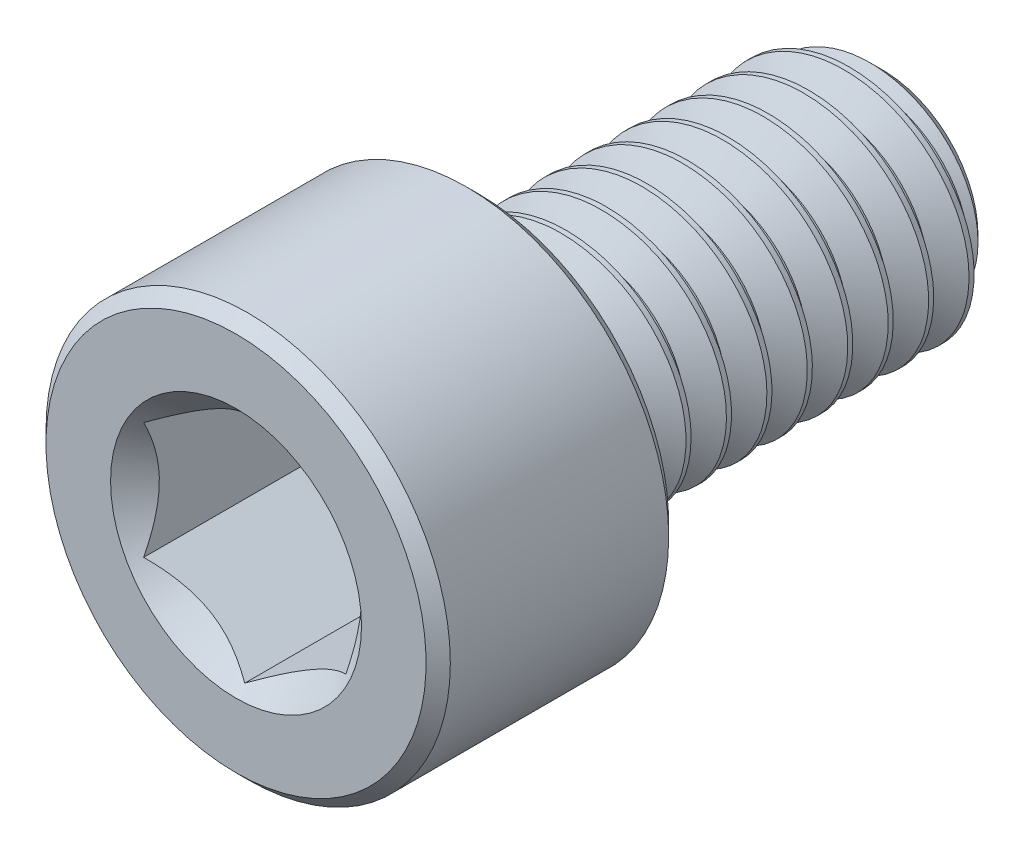
SolidWorks part; units mm, degrees
ref_plane "Front Plane" through (0, 0, 0) normal (0, 0, 1) x (1, 0, 0)
ref_plane "Top Plane" through (0, 0, 0) normal (0, 1, 0) x (1, 0, 0)
ref_plane "Right Plane" through (0, 0, 0) normal (1, 0, 0) x (0, 0, -1)
sketch "Sketch1" plane through (0, 0, 0) normal (1, 0, 0) x (0, 0, -1)
  line L0 (-8, 0) -> (8, 0) construction
  line L1 (8, 0) -> (8, 2.3505) construction
  line L2 (8, 2.3505) -> (7.3505, 3) construction
  line L3 (7.3505, 3) -> (7.25, 3) construction
  line L4 (7.25, 3) -> (-2, 3) construction
  line L5 (-2, 3) -> (-2, 5) construction
  line L6 (-2, 5) -> (-8, 5) construction
  line L7 (-8, 5) -> (-8, 0) construction
  line L8 (8, 2.3505) -> (8, 3) construction
  line L9 (7.9375, 3.1083) -> (8.4375, 2.2422) construction
  line L10 (8.4375, 2.2422) -> (8.9375, 3.1083) construction
  line L11 (8.9375, 3.1083) -> (7.9375, 3.1083) construction
  line L12 (8.4375, 3.1083) -> (8.4375, 3) construction
  line L13 (8.4375, 2.2422) -> (8.4375, 2.3505) construction
  line L14 (8.375, 2.3505) -> (8.5, 2.3505) construction
  line L15 (8, 3) -> (8.875, 3) construction
  line L16 (7.9687, 3.0541) -> (8.9063, 3.0541) construction
  line L17 (8, 0) -> (8, -3) construction
  line L18 (-2.3, 5) -> (-2, 4.7) construction
  line L19 (-7.7, 5) -> (-8, 4.7) construction
  line L20 (-2, 3) -> (-2, 0) construction
  line L21 (-2, 1.5) -> (1.3333, 1.5) construction
  line L22 (1.3333, 1.5) -> (4.6667, 1.5) construction
  line L23 (4.6667, 1.5) -> (8, 1.5) construction
  line L24 (1.3333, 1.5) -> (1.3333, 3) construction
  line L25 (1.3333, 3) -> (1.3333, 5) construction
  line L26 (4.6667, 1.5) -> (4.6667, 5) construction
  point P0 (-8, 2.5)
  point P3 (5.5, 3)
  point P4 (0, 0)
  point P18 (4.6667, 3)
  point P22 (8.4375, 2.3505)
  point P24 (7.25, 3)
  point P25 (8.4375, 3)
  point P28 (8.4375, 3.0541)
  point P29 (5.5, -3)
  point P30 (1.3333, 3)
  point P31 (-5, 5)
  point P37 (-3.05, 5)
  point P38 (-7.55, 5)
  point P45 (1.3333, 1.5)
  point P46 (4.6667, 1.5)
  dimension "D2" = 0.125
  dimension "D7" = 0.3
  dimension "D8" = 0.3
  dimension "D9" = 0.3
  dimension "D10" = 0.15
  dimension "D11" = 0.75
  dimension "Drive Size" = 5
  dimension "Head Diameter" = 10
  dimension "Head Height" = 6
  dimension "Thread Pitch" = 1
  dimension "Thread Dia" = 6
  dimension "Length" = 10
  dimension "D12" = 0.75
  dimension "D4" = 2.5
  dimension "D3" = 45
sketch "Sketch2" plane through (0, 0, 0) normal (1, 0, 0) x (0, 0, -1)
  line L0 (-8, 0) -> (-8, 4.7)
  line L1 (-7.7, 5) -> (-2.3, 5)
  line L2 (-2, 4.7) -> (-2, 3.3)
  line L4 (7.3505, 3) -> (8, 2.3505)
  line L5 (8, 2.3505) -> (8, 0)
  line L6 (-2, 5) -> (-8, 5) construction
  line L7 (8, 0) -> (-8, 0)
  line L8 (-7.7, 5) -> (-8, 4.7) construction
  line L10 (-7.7, 5) -> (-8, 4.7)
  line L14 (-2.3, 5) -> (-2, 4.7) construction
  line L16 (-2.3, 5) -> (-2, 4.7)
  line L17 (-2, 3) -> (-2, 5) construction
  line L19 (-1.7, 3) -> (7.3505, 3)
  line L20 (7.25, 3) -> (-2, 3) construction
  arc A1 (-2, 3.3) -> (-1.7, 3) centre (-1.7, 3.3) ccw
  dimension "D3" = 0.3
revolve "Revolve1" add sketch "Sketch2" angle 360 about L7
sketch "Sketch3" plane through (0, 0, 8) normal (0, 0, 1) x (1, 0, 0)
  line L1 (2.5, -1.4434) -> (2.5, 1.4434)
  line L2 (2.5, 1.4434) -> (0, 2.8868)
  line L3 (0, 2.8868) -> (-2.5, 1.4434)
  line L4 (-2.5, 1.4434) -> (-2.5, -1.4434)
  line L5 (-2.5, -1.4434) -> (0, -2.8868)
  line L6 (0, -2.8868) -> (2.5, -1.4434)
  circle A0 centre (0, 0) radius 2.5 construction
  circle A1 centre (0, 0) radius 5 construction
  circle A2 centre (0, 0) radius 5 construction
  circle A3 centre (0, 0) radius 2.8868 construction
  point P13 (0, 0)
  dimension "D1" = 5.7735
extrude "Cut-Extrude1" cut sketch "Sketch3" against normal offset from surface (5 mm away) 1 up to face at (0, 4.7, 2)
sketch "Sketch4" plane through (0, 0, 8) normal (0, 0, 1) x (1, 0, 0)
  circle A0 centre (0, 0) radius 3.1033
  dimension "D1" = 6.2065
extrude "Cut-Extrude2" cut sketch "Sketch4" against normal up to vertex (3 mm away) draft 45 up to point (0, 5, 5)
sketch "Sketch11" plane through (0, 0, 0) normal (1, 0, 0) x (0, 0, -1)
  line L0 (-8, 0) -> (8, 0) construction
  line L1 (-8, 0) -> (8, 0) construction
  line L2 (-0.125, 0) -> (-0.125, 3) construction
  line L3 (7.25, 3) -> (-2, 3) construction
  line L4 (6.125, 0) -> (6.125, 3) construction
  line L6 (8, 2.3505) -> (8, 3) construction
  point P2 (-0.125, 0)
  point P3 (6.125, 0)
  dimension "D1" = 1.875
  dimension "D2" = 1.875
sketch "Sketch6" plane through (0, 0, -8) normal (0, 0, -1) x (-1, 0, 0)
  circle A0 centre (0, 0) radius 3
curve "Helix/Spiral1" pitch 1 height 11 turns 11
sketch "Sketch10" plane through (0, 0, 0) normal (1, 0, 0) x (0, 0, -1)
  line L0 (-1.7, -5) -> (-1.7, 5)
  line L5 (-8, 0) -> (8, 0) construction
  line L6 (-1.7, 3) -> (-1.7, -3) construction
  point P3 (-1.7, 0)
split "Split1" trim tools "Sketch10" bodies to split 106 resulting bodies 114 115
sketch "Sketch7" plane through (0, 0, 0) normal (1, 0, 0) x (0, 0, -1)
  line L0 (7.9687, 3.0541) -> (8.9063, 3.0541)
  line L1 (8.9063, 3.0541) -> (8.5, 2.3505)
  line L2 (8.5, 2.3505) -> (8.375, 2.3505)
  line L3 (8.375, 2.3505) -> (7.9687, 3.0541)
sweep "Cut-Sweep1" cut profiles "Sketch7" path "Helix/Spiral1" align with end faces yes
sketch "Sketch8" plane through (0, 0, 0) normal (1, 0, 0) x (0, 0, -1)
  line L0 (-2, 0) -> (-2, 3)
  line L1 (-1.7, -3) -> (-1.7, 3) construction
  line L2 (-2, 3) -> (-1.7, 3)
  line L4 (-1.7, 3) -> (0.0321, 0)
  line L5 (0.0321, 0) -> (-2, 0)
  line L6 (7.25, 3) -> (-2, 3) construction
  line L7 (-8, 0) -> (8, 0) construction
  dimension "D1" = 60
revolve "Revolve2" add sketch "Sketch8" angle 360 about L5
equation "\"D2@Sketch1\" = \"Thread Pitch@Sketch1\" / 8"
equation "\"D4@Helix/Spiral1\" = \"Thread Pitch@Sketch1\""
equation "\"D7@Sketch1\" = \"Head Height@Sketch1\" * .05"
equation "\"D8@Sketch1\"=\"D7@Sketch1\""
equation "\"D9@Sketch1\"=\"D7@Sketch1\""
equation "\"D10@Sketch1\"=\"D7@Sketch1\"/2"
equation "\"D11@Sketch1\"=\"D10@Sketch1\"*5"
equation "\"D4@Sketch1\"=\"Thread Pitch@Sketch1\"*2.5"
equation "\"D12@Sketch1\"=\"Thread Pitch@Sketch1\"*.75"
equation "\"D3@Helix/Spiral1\"=\"Length@Sketch1\"+\"Thread Pitch@Sketch1\""
equation "\"D3@Sketch2\"=\"Thread Dia@Sketch1\"*0.05"
equation "\"D1@Sketch11\"=\"Length@Sketch1\"*0.1875"
equation "\"D2@Sketch11\"=\"D1@Sketch11\""
equation "\"D1@Sketch4\"=\"D1@Sketch3\"*1.075"
